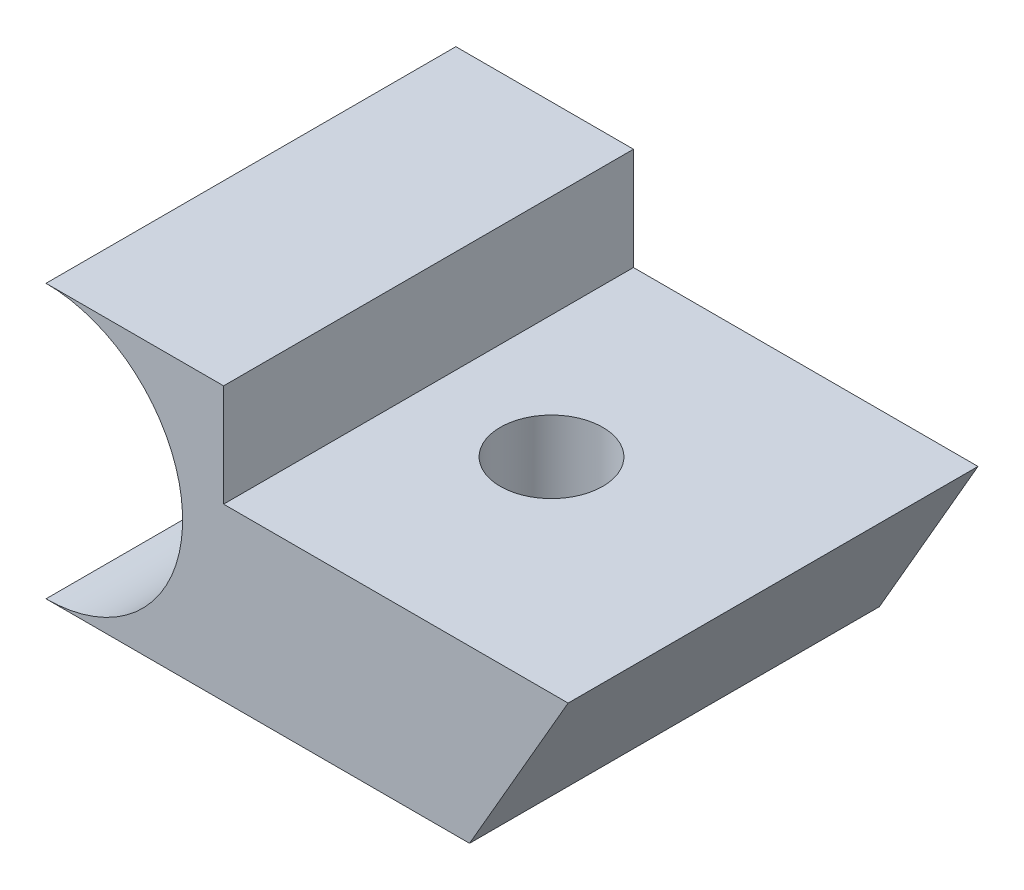
SolidWorks part; units mm, degrees
ref_plane "Front Plane" through (0, 0, 0) normal (0, 0, 1) x (1, 0, 0)
ref_plane "Top Plane" through (0, 0, 0) normal (0, 1, 0) x (1, 0, 0)
ref_plane "Right Plane" through (0, 0, 0) normal (1, 0, 0) x (0, 0, -1)
sketch "Sketch1" plane through (0, 0, 0) normal (0, 0, 1) x (1, 0, 0)
  line L1 (0, 0) -> (50.8, 0)
  line L3 (0, 25.4) -> (16.51, 25.4)
  line L4 (50.8, 0) -> (50.8, 15.875)
  line L6 (16.51, 25.4) -> (16.51, 15.875)
  line L7 (16.51, 15.875) -> (50.8, 15.875)
  arc A1 (0, 0) -> (0, 25.4) centre (0, 12.7) ccw
  dimension "D2" = 25.4
  dimension "D1" = 50.8
  dimension "D3" = 9.525
  dimension "D4" = 16.51
extrude "Boss-Extrude1" add sketch "Sketch1" along normal blind 38.1
chamfer "Chamfer1" distance 11.43 angle 60 1 edges at (50.8, 0, 19.05) first distance on face at (25.4, 0, 19.05)
hole_wizard "3/8 (0.375) Diameter Hole1" positions "Sketch5" profile "Sketch3" hole size "3/8" standard "ANSI Inch" end condition through all
sketch "Sketch5" plane through (0, 25.4, 0) normal (0, 1, 0) x (1, 0, 0)
  line L1 (48.5354, -38.1) -> (48.5354, 0) construction
  point P0 (27.94, -19.05)
  dimension "D1" = 20.5954
sketch "Sketch3" plane through (27.94, 25.4, 19.05) normal (1, 0, 0) x (0, 0, 1)
  line L0 (0, 0) -> (0, 25.4)
  line L1 (0, 25.4) -> (4.7625, 25.4)
  line L2 (4.7625, 25.4) -> (4.7625, 0)
  line L5 (4.7625, 0) -> (0, 0)
  line L11 (0, -6.35) -> (0, 107.95) construction
  dimension "Thru Hole Dia." = 9.525
  dimension "Thru Hole Depth" = 25.4
